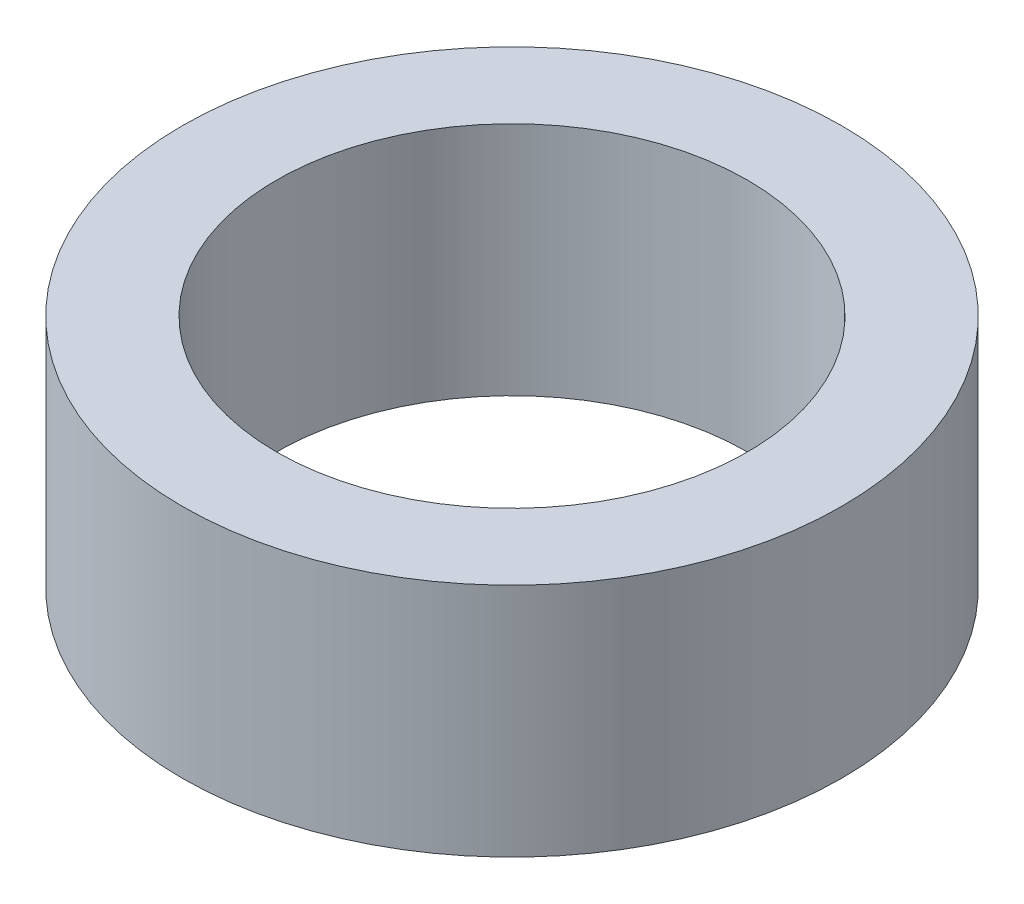
SolidWorks part; units mm, degrees
ref_plane "Front Plane" through (0, 0, 0) normal (0, 0, 1) x (1, 0, 0)
ref_plane "Top Plane" through (0, 0, 0) normal (0, 1, 0) x (1, 0, 0)
ref_plane "Right Plane" through (0, 0, 0) normal (1, 0, 0) x (0, 0, -1)
sketch "Sketch1" plane through (0, 0, 0) normal (0, 1, 0) x (1, 0, 0)
  circle A0 centre (0, 0) radius 35
  dimension "FLANGE_OD" = 70
extrude "Boss-Extrude1" add sketch "Sketch1" along normal blind 25
sketch "Sketch2" plane through (0, 0, 0) normal (0, 1, 0) x (1, 0, 0)
  circle A0 centre (0, 0) radius 25
  dimension "BORE_D" = 50
extrude "Cut-Extrude1" cut sketch "Sketch2" along normal through all
sketch "Sketch3" plane through (0, 25, 0) normal (0, 1, 0) x (1, 0, 0)
  circle A0 centre (0, 0) radius 15.5179 construction
  circle A1 centre (-15.5179, 0) radius 1.7831
  dimension "BOLT_D" = 3.5662
  dimension "BOLT_PCD" = 31.0357
extrude "Cut-Extrude2" cut sketch "Sketch3" against normal blind 19.78 rebuild error yes
pattern_circular "CirPattern1" count 3 over 360 rebuild error yes
